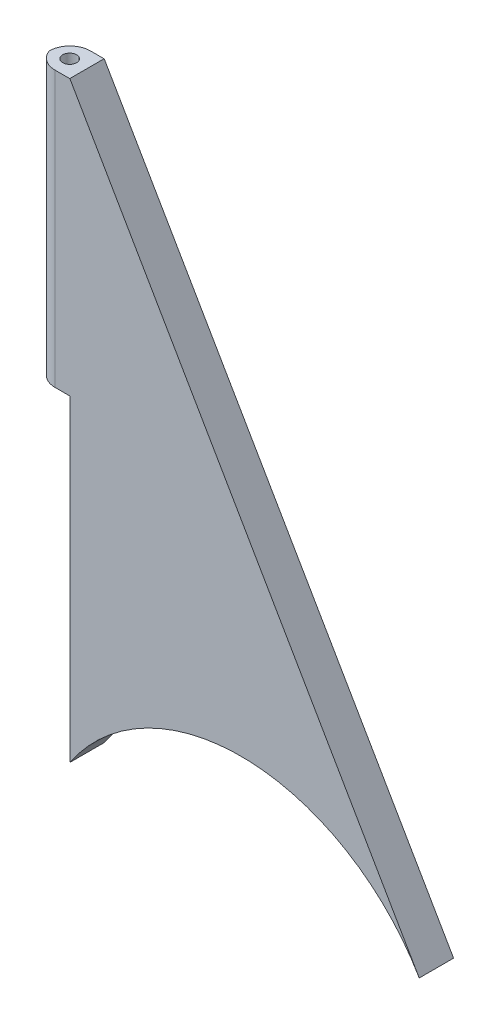
SolidWorks part; units mm, degrees
ref_plane "Plan de face" through (0, 0, 0) normal (0, 0, 1) x (1, 0, 0)
ref_plane "Plan de dessus" through (0, 0, 0) normal (0, 1, 0) x (1, 0, 0)
ref_plane "Plan de droite" through (0, 0, 0) normal (1, 0, 0) x (0, 0, -1)
sketch "Esquisse1" plane through (0, 0, 0) normal (0, 0, 1) x (1, 0, 0)
  line L0 (26.025, -0.448) -> (-24.8298, 87.5088)
  line L1 (-24.8298, 87.5088) -> (-24.8298, 1.2934)
  arc A0 (26.025, -0.448) -> (-24.8298, 1.2934) centre (0.0536, -15.4641) ccw
  dimension "D1" = 30
extrude "Boss.-Extru.1" add sketch "Esquisse1" along normal blind 5 contours L1 A0 L0
ref_plane "Plan3" through (0, 87.4899, 0) normal (0, 1, 0) x (1, 0, 0)
sketch "Esquisse9" plane through (0, 87.4899, 0) normal (0, 1, 0) x (1, 0, 0)
  line L0 (-24.8298, -5) -> (-24.8298, 0)
  line L1 (-24.8298, -5) -> (-29.8298, -5)
  line L2 (-24.8298, 0) -> (-29.8298, 0)
  line L3 (-29.8298, -5) -> (-29.8298, 0)
  dimension "D1" = 5
  dimension "D2" = 5
extrude "Boss.-Extru.3" add sketch "Esquisse9" against normal blind 40
sketch "Esquisse10" plane through (0, 87.4899, 0) normal (0, 1, 0) x (1, 0, 0)
sketch "Esquisse11" plane through (0, 87.4899, 0) normal (0, 1, 0) x (1, 0, 0)
  circle A1 centre (-27.3532, -2.5) radius 1.0093
extrude "Enlèv. mat.-Extru.2" cut sketch "Esquisse11" against normal blind 40
fillet "Congé1" radius 3 1 edges at (-29.8298, 67.4899, 0)
fillet "Congé2" radius 3 1 edges at (-29.8298, 67.4899, 5)
